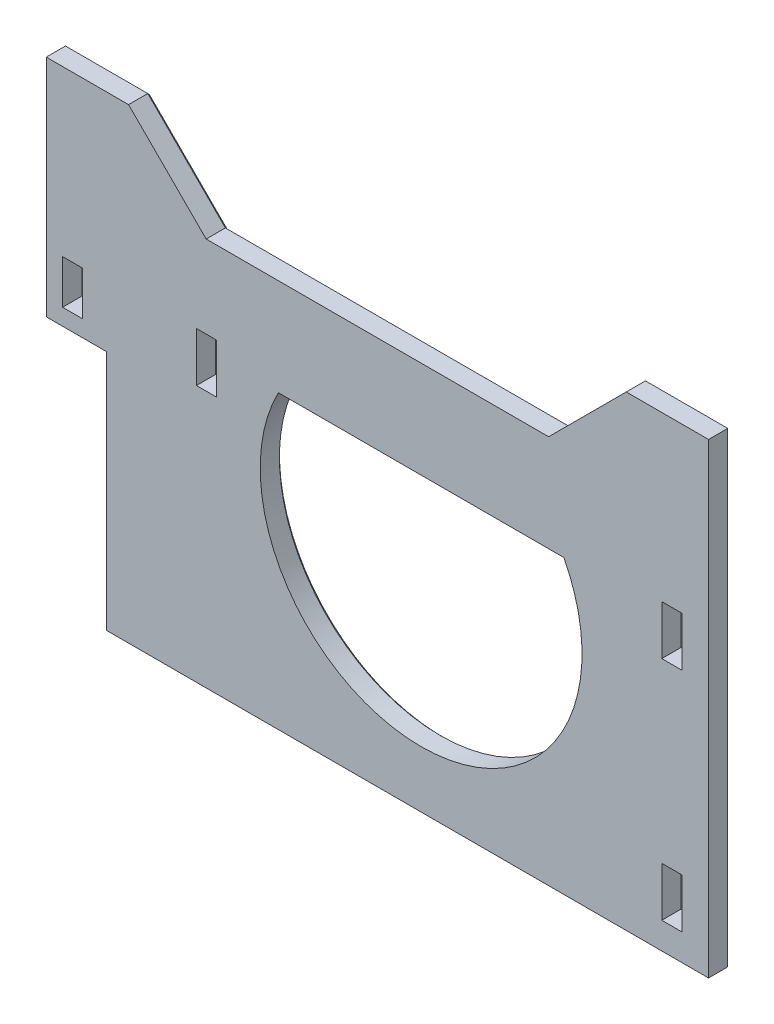
SolidWorks part; units mm, degrees
ref_plane "Front Plane" through (0, 0, 0) normal (0, 0, 1) x (1, 0, 0)
ref_plane "Top Plane" through (0, 0, 0) normal (0, 1, 0) x (1, 0, 0)
ref_plane "Right Plane" through (0, 0, 0) normal (1, 0, 0) x (0, 0, -1)
sketch "Sketch1" plane through (0, 0, 0) normal (0, 0, 1) x (1, 0, 0)
  line L0 (-25.9, 23.1791) -> (26.1356, 23.1791)
  line L6 (-40.825, 25.85) -> (-37.175, 25.85)
  line L9 (-40.825, 25.85) -> (-40.825, 16.85)
  line L12 (-40.825, 16.85) -> (-37.175, 16.85)
  line L15 (-37.175, 25.85) -> (-37.175, 16.85)
  line L51 (52.5, 30) -> (52.5, -30)
  line L54 (43.975, 25.15) -> (47.625, 25.15)
  line L55 (43.975, 25.15) -> (43.975, 16.15)
  line L56 (43.975, 16.15) -> (47.625, 16.15)
  line L57 (47.625, 25.15) -> (47.625, 16.15)
  line L58 (47.625, -16.15) -> (43.975, -16.15)
  line L59 (47.625, -16.15) -> (47.625, -25.15)
  line L60 (47.625, -25.15) -> (43.975, -25.15)
  line L61 (43.975, -16.15) -> (43.975, -25.15)
  line L65 (-65.225, 25) -> (-61.575, 25)
  line L66 (-65.225, 25) -> (-65.225, 17)
  line L67 (-65.225, 17) -> (-61.575, 17)
  line L68 (-61.575, 25) -> (-61.575, 17)
  line L76 (52.5, 30) -> (-68.2, 30)
  line L81 (-39, 25.85) -> (-39, 16.85) construction
  line L82 (-37.175, 21.35) -> (-40.825, 21.35) construction
  line L83 (-63.4, 25) -> (-63.4, 17) construction
  line L84 (-61.575, 21) -> (-65.225, 21) construction
  line L85 (47.625, 20.65) -> (43.975, 20.65) construction
  line L86 (45.8, 25.15) -> (45.8, 16.15) construction
  line L87 (45.8, -16.15) -> (45.8, -25.15) construction
  line L88 (47.625, -20.65) -> (43.975, -20.65) construction
  line L89 (-57.2, -30) -> (-57.2, 14)
  line L90 (-57.2, 14) -> (-68.2, 14)
  line L91 (-68.2, 14) -> (-68.2, 30)
  line L92 (-57.2, -30) -> (52.5, -30)
  arc A12 (-25.9, 23.1791) -> (26.1356, 23.1791) centre (0.1178, 9.6488) ccw
  point P0 (0, 0)
  point P14 (52.5, 0)
  point P25 (-7.85, 30)
  dimension "D3" = 3.65
  dimension "D4" = 9
  dimension "D6" = 60
  dimension "D5" = 24.4
  dimension "D7" = 53.65
  dimension "D2" = 31.15
  dimension "D10" = 20.65
  dimension "D11" = 20.65
  dimension "D8" = 120.7
  dimension "D9" = 11
  dimension "D12" = 44
extrude "Boss-Extrude1" add sketch "Sketch1" along normal blind 4
sketch "Sketch2" plane through (0, 0, 0) normal (0, 0, 1) x (1, 0, 0)
  line L0 (-68.2, 30) -> (52.5, 30)
  line L4 (23.3579, 40.8579) -> (-39.0579, 40.8579)
  line L5 (-39.0579, 40.8579) -> (-53.2, 55)
  line L6 (-53.2, 55) -> (-68.2, 55)
  line L7 (-68.2, 55) -> (-68.2, 30)
  line L8 (23.3579, 40.8579) -> (37.5, 55)
  line L9 (37.5, 55) -> (52.5, 55)
  line L10 (52.5, 55) -> (52.5, 30)
  line L12 (-68.2, 30) -> (-68.2, 14) construction
  dimension "D1" = 25
  dimension "D2" = 20
  dimension "D3" = 15
  dimension "D4" = 135
extrude "Boss-Extrude2" add sketch "Sketch2" along normal blind 4
sketch "Sketch3" plane through (0, 0, 0) normal (0, 0, -1) x (-1, 0, 0)
  line L0 (-45.8, 25.15) -> (-45.8, 16.15) construction
  line L1 (-47.625, 25.15) -> (-43.975, 25.15) construction
  line L2 (-43.975, 16.15) -> (-47.625, 16.15) construction
  line L3 (-47.625, 20.65) -> (-43.975, 20.65) construction
  line L4 (-47.625, 16.15) -> (-47.625, 25.15) construction
  line L5 (-43.975, 25.15) -> (-43.975, 16.15) construction
  line L6 (-45.8, -16.15) -> (-45.8, -25.15) construction
  line L7 (-47.625, -16.15) -> (-43.975, -16.15) construction
  line L8 (-43.975, -25.15) -> (-47.625, -25.15) construction
  line L9 (-47.625, -20.65) -> (-43.975, -20.65) construction
  line L10 (-47.625, -25.15) -> (-47.625, -16.15) construction
  line L11 (-43.975, -16.15) -> (-43.975, -25.15) construction
  line L12 (39, 25.85) -> (39, 16.85) construction
  line L13 (37.175, 25.85) -> (40.825, 25.85) construction
  line L14 (40.825, 16.85) -> (37.175, 16.85) construction
  line L15 (37.175, 21.35) -> (40.825, 21.35) construction
  line L16 (37.175, 16.85) -> (37.175, 25.85) construction
  line L17 (40.825, 25.85) -> (40.825, 16.85) construction
  line L18 (63.4, 25) -> (63.4, 17) construction
  line L19 (61.575, 25) -> (65.225, 25) construction
  line L20 (65.225, 17) -> (61.575, 17) construction
  line L21 (61.575, 21) -> (65.225, 21) construction
  line L22 (61.575, 17) -> (61.575, 25) construction
  line L23 (65.225, 25) -> (65.225, 17) construction
chamfer "Chamfer1" distance 0.5 angle 45 28 edges at (45.8, -25.15, 0) (43.975, -20.65, 0) (45.8, -16.15, 0) (47.625, -20.65, 0) (-63.4, 25, 0) (-61.575, 21, 0) (-63.4, 17, 0) (-65.225, 21, 0) (0.1178, 23.1791, 0) (0.1178, -19.6769, 0) (-62.7, 14, 0) (-57.2, -8, 0) (-2.35, -30, 0) (52.5, 12.5, 0) (45, 55, 0) (30.4289, 47.9289, 0) (-7.85, 40.8579, 0) (-46.1289, 47.9289, 0) (-60.7, 55, 0) (-68.2, 34.5, 0) (-39, 25.85, 0) (-37.175, 21.35, 0) (-39, 16.85, 0) (-40.825, 21.35, 0) (45.8, 25.15, 0) (47.625, 20.65, 0) (45.8, 16.15, 0) (43.975, 20.65, 0)
equation "\"pin_hole_width\"=3.65"
equation "\"D3@Sketch1\"=\"pin_hole_width\""
equation "\"pin_hole_height\"=9"
equation "\"D4@Sketch1\"=\"pin_hole_height\""
